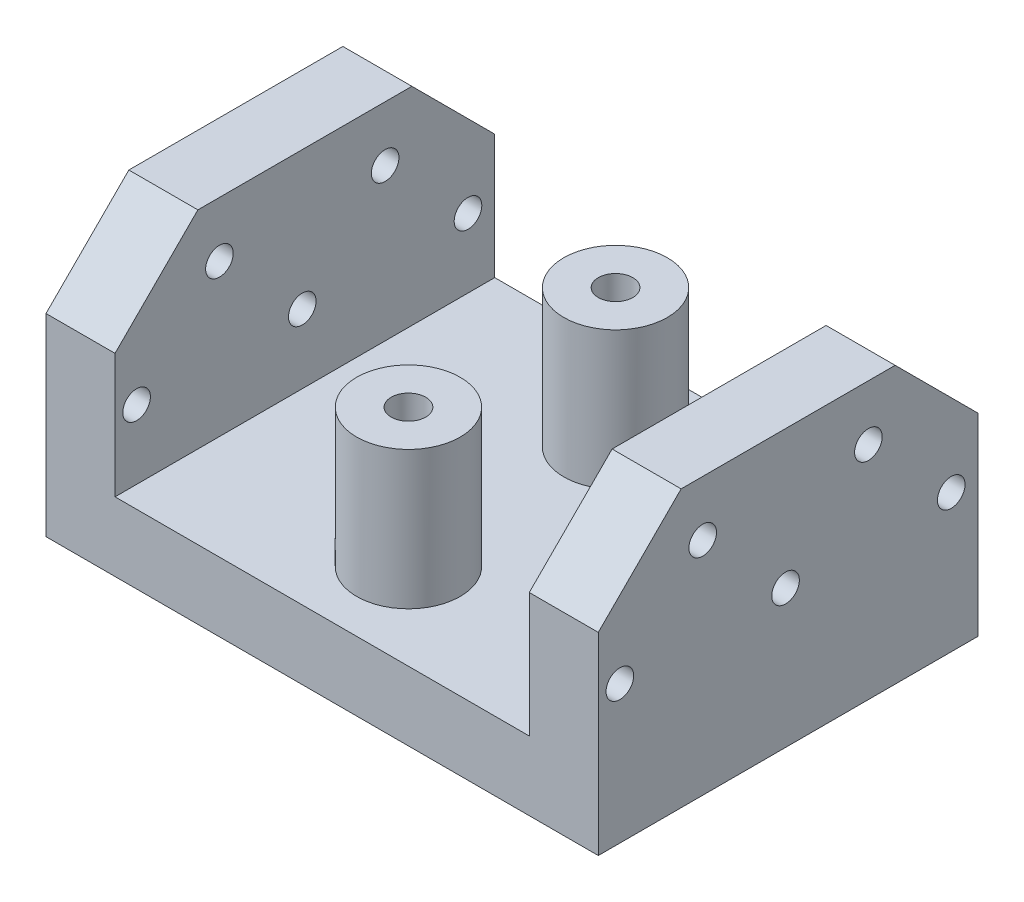
SolidWorks part; units mm, degrees
ref_plane "Front Plane" through (0, 0, 0) normal (0, 0, 1) x (1, 0, 0)
ref_plane "Top Plane" through (0, 0, 0) normal (0, 1, 0) x (1, 0, 0)
ref_plane "Right Plane" through (0, 0, 0) normal (1, 0, 0) x (0, 0, -1)
sketch "Sketch1" plane through (0, 0, 0) normal (0, 1, 0) x (1, 0, 0)
  line L1 (-40, -27.5) -> (40, -27.5)
  line L2 (-40, -27.5) -> (-40, 27.5)
  line L3 (-40, 27.5) -> (40, 27.5)
  line L4 (40, -27.5) -> (40, 27.5)
  line L5 (-40, -27.5) -> (40, 27.5) construction
  line L6 (-40, 27.5) -> (40, -27.5) construction
  point P0 (0, 0)
  dimension "D1" = 80
  dimension "D2" = 55
extrude "Boss-Extrude1" add sketch "Sketch1" along normal blind 10
sketch "Sketch2" plane through (0, 10, 0) normal (0, 1, 0) x (1, 0, 0)
  line L0 (-40, -27.5) -> (40, -27.5) construction
  line L1 (-40, 27.5) -> (-30, 27.5)
  line L2 (-40, 27.5) -> (-40, -27.5)
  line L3 (-40, -27.5) -> (-30, -27.5)
  line L4 (-30, 27.5) -> (-30, -27.5)
  line L6 (40, 27.5) -> (30, 27.5)
  line L7 (40, 27.5) -> (40, -27.5)
  line L8 (40, -27.5) -> (30, -27.5)
  line L9 (30, 27.5) -> (30, -27.5)
  dimension "D1" = 10
  dimension "D2" = 10
extrude "Boss-Extrude2" add sketch "Sketch2" along normal blind 30
sketch "Sketch3" plane through (-40, 0, 0) normal (-1, 0, 0) x (0, 0, 1)
  line L0 (-24.4564, 20) -> (25.208, 20) construction
  line L1 (-27.5, 0) -> (27.5, 0) construction
  line L2 (-23.6242, 32) -> (24.3758, 32) construction
  circle A0 centre (-23.6242, 20) radius 2
  circle A1 centre (0.3758, 20) radius 2
  circle A2 centre (24.3758, 20) radius 2
  circle A3 centre (-11.6242, 32) radius 2
  circle A4 centre (12.3758, 32) radius 2
  dimension "D1" = 4
  dimension "D2" = 4
  dimension "D3" = 4
  dimension "D8" = 4
  dimension "D9" = 4
  dimension "D4" = 24
  dimension "D5" = 24
  dimension "D6" = 20
  dimension "D7" = 12
  dimension "D10" = 12
  dimension "D11" = 12
extrude "Cut-Extrude1" cut sketch "Sketch3" against normal through all
sketch "Sketch4" plane through (0, 0, 0) normal (0, -1, 0) x (1, 0, 0)
  line L0 (-29.1816, 0) -> (32.7136, 0) construction
  line L1 (0, 21.9913) -> (0, -22.58) construction
  circle A0 centre (0, 15) radius 2.5
  circle A1 centre (0, -15) radius 2.5
  point P9 (0, 0)
  dimension "D1" = 5
  dimension "D2" = 5
  dimension "D3" = 15
  dimension "D4" = 15
extrude "Cut-Extrude2" cut sketch "Sketch4" against normal blind 30
sketch "Sketch5" plane through (0, 10, 0) normal (0, 1, 0) x (1, 0, 0)
  circle A0 centre (0, -15) radius 2.5 construction
  circle A1 centre (0, 15) radius 2.5 construction
  circle A2 centre (0, -15) radius 2.5
  circle A3 centre (0, 15) radius 2.5
  circle A4 centre (0, 15) radius 7.5
  circle A5 centre (0, -15) radius 7.5
  dimension "D1" = 15
  dimension "D2" = 15
extrude "Boss-Extrude3" add sketch "Sketch5" along normal blind 20
sketch "Sketch6" plane through (0, 0, 0) normal (0, -1, 0) x (1, 0, 0)
  line L0 (0, 15) -> (0, 10.75) construction
  line L1 (0, -15) -> (0, -10.75) construction
  line L2 (-10.25, 10.75) -> (10.25, 10.75)
  line L3 (-10.25, -10.75) -> (10.25, -10.75)
  line L4 (-10.25, 10.75) -> (-10.25, 7.5)
  line L5 (-10.25, 7.5) -> (10.25, 7.5)
  line L6 (10.25, 7.5) -> (10.25, 10.75)
  line L7 (-10.25, -10.75) -> (-10.25, -7.5)
  line L8 (-10.25, -7.5) -> (10.25, -7.5)
  line L9 (10.25, -7.5) -> (10.25, -10.75)
  dimension "D1" = 4.25
  dimension "D2" = 4.25
  dimension "D3" = 20.5
  dimension "D4" = 20.5
  dimension "D5" = 10.25
  dimension "D6" = 10.25
  dimension "D7" = 3.25
  dimension "D8" = 3.25
extrude "Cut-Extrude3" cut sketch "Sketch6" against normal blind 5
sketch "Sketch7" plane through (40, 0, 0) normal (1, 0, 0) x (0, 0, -1)
  line L0 (-27.5, 28) -> (-15.5, 40)
  line L1 (-27.5, 40) -> (-27.5, 0) construction
  line L2 (-27.5, 40) -> (27.5, 40) construction
  line L3 (15.5, 40) -> (27.5, 28)
  line L4 (27.5, 40) -> (27.5, 0) construction
  line L5 (-27.5, 28) -> (-27.5, 40)
  line L6 (-27.5, 40) -> (-15.5, 40)
  line L7 (15.5, 40) -> (27.5, 40)
  line L8 (27.5, 40) -> (27.5, 28)
  dimension "D1" = 12
  dimension "D2" = 12
  dimension "D3" = 12
extrude "Cut-Extrude4" cut sketch "Sketch7" against normal through all
